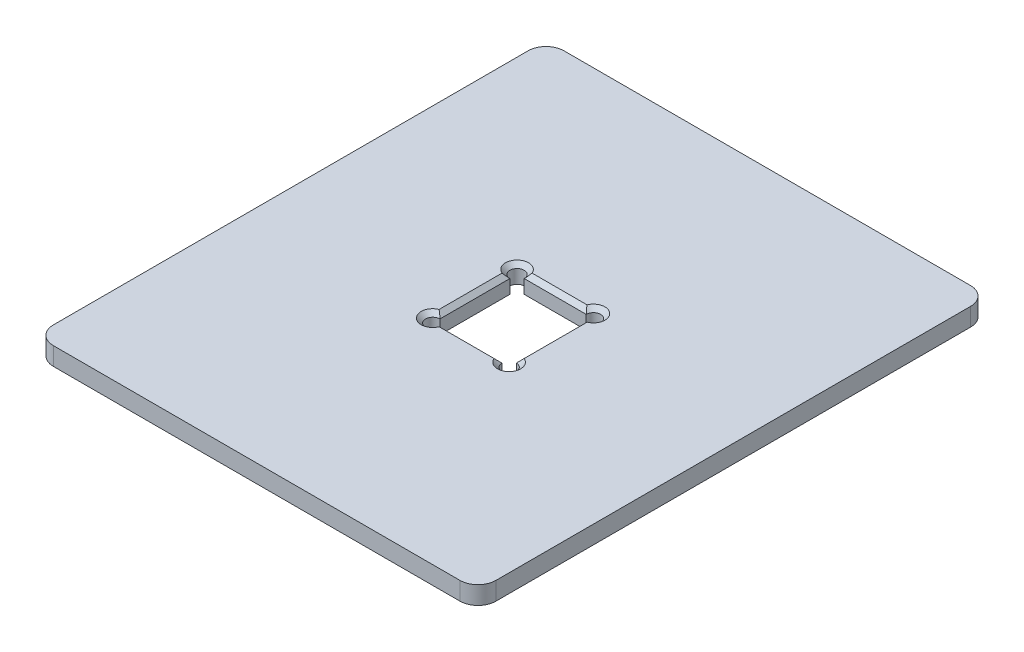
SolidWorks part; units mm, degrees
ref_plane "Front Plane" through (0, 0, 0) normal (0, 0, 1) x (1, 0, 0)
ref_plane "Top Plane" through (0, 0, 0) normal (0, 1, 0) x (1, 0, 0)
ref_plane "Right Plane" through (0, 0, 0) normal (1, 0, 0) x (0, 0, -1)
sketch "Sketch1" plane through (0, 0, 0) normal (0, 1, 0) x (1, 0, 0)
  line L1 (-39, 45) -> (39, 45)
  line L2 (-39, 45) -> (-39, -45)
  line L3 (-39, -45) -> (39, -45)
  line L4 (39, 45) -> (39, -45)
  line L5 (-5.334, 7.493) -> (5.588, 7.493)
  line L6 (-6.604, 6.223) -> (-6.604, -6.096)
  line L7 (-5.334, -7.366) -> (5.588, -7.366)
  line L8 (6.858, 6.223) -> (6.858, -6.096)
  arc A0 (-5.334, 7.493) -> (-6.604, 6.223) centre (-6.604, 7.493) ccw
  arc A1 (6.858, 6.223) -> (5.588, 7.493) centre (6.858, 7.493) ccw
  arc A2 (5.588, -7.366) -> (6.858, -6.096) centre (6.858, -7.366) ccw
  arc A3 (-6.604, -6.096) -> (-5.334, -7.366) centre (-6.604, -7.366) ccw
  dimension "D9" = 2.54
  dimension "D10" = 2.54
  dimension "D11" = 2.54
  dimension "D12" = 2.54
  dimension "D1" = 78
  dimension "D2" = 90
  dimension "D3" = 39
  dimension "D4" = 45
  dimension "D5" = 13.462
  dimension "D6" = 6.858
  dimension "D7" = 14.859
  dimension "D8" = 7.366
extrude "Boss-Extrude1" add sketch "Sketch1" along normal blind 3.175
fillet "Fillet1" radius 3.175 4 edges at (-39, 1.5875, -45) (39, 1.5875, -45) (39, 1.5875, 45) (-39, 1.5875, 45)
chamfer "Chamfer1" distance 0.762 angle 45 8 edges at (-6.604, 3.175, -0.0635) (-7.502, 3.175, 8.264) (0.127, 3.175, 7.366) (7.756, 3.175, 8.264) (6.858, 3.175, -0.0635) (7.756, 3.175, -8.391) (0.127, 3.175, -7.493) (-7.502, 3.175, -8.391)
